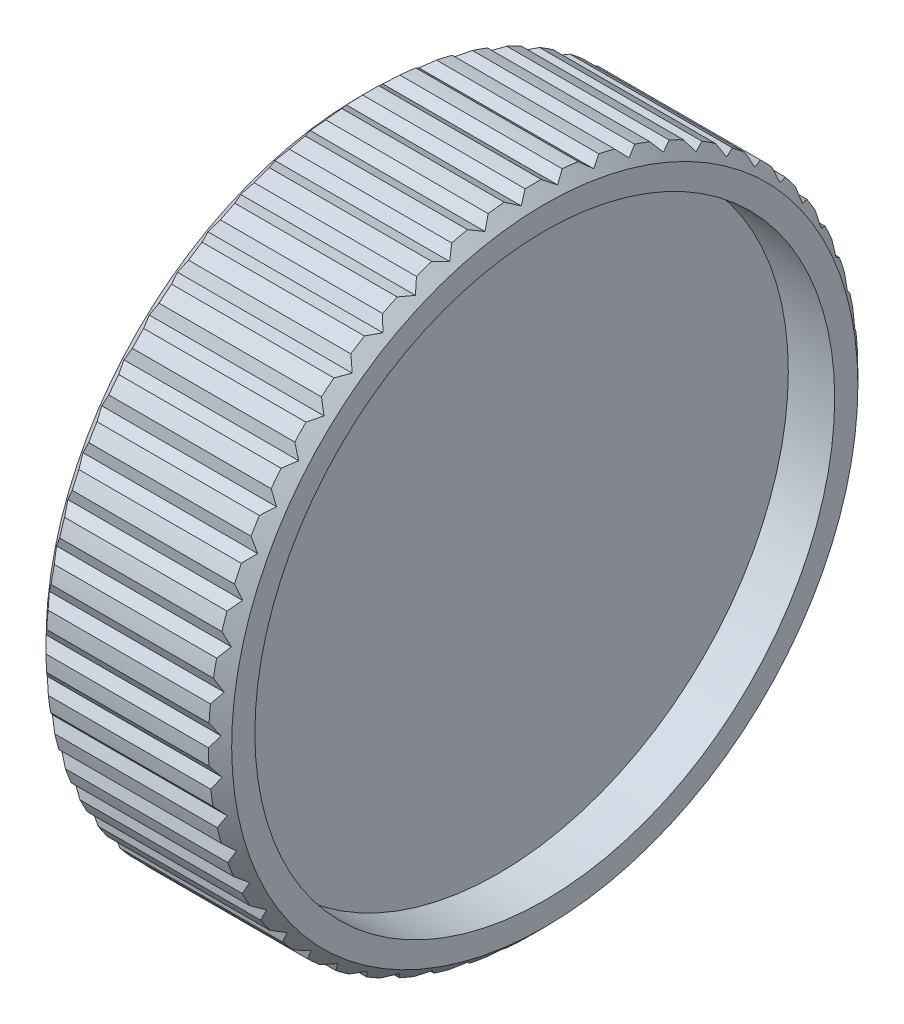
SolidWorks part; units mm, degrees
ref_plane "Front Plane" through (0, 0, 0) normal (0, 0, 1) x (1, 0, 0)
ref_plane "Top Plane" through (0, 0, 0) normal (0, 1, 0) x (1, 0, 0)
ref_plane "Right Plane" through (0, 0, 0) normal (1, 0, 0) x (0, 0, -1)
sketch "Sketch1" plane through (0, 0, 0) normal (1, 0, 0) x (0, 0, -1)
  circle A0 centre (0, 0) radius 28
  dimension "D1" = 56
extrude "Boss-Extrude1" add sketch "Sketch1" along normal mid plane 16
sketch "Sketch2" plane through (8, 0, 0) normal (1, 0, 0) x (0, 0, -1)
  circle A0 centre (0, 38) radius 15
  dimension "D1" = 30
  dimension "D2" = 38
extrude "Cut-Extrude1" [suppressed] cut sketch "Sketch2" against normal through all
chamfer "Chamfer1" distance 1 angle 45 2 edges at (-8, 0, -28) (8, 0, -28)
sketch "Sketch3" plane through (8, 0, 0) normal (1, 0, 0) x (0, 0, -1)
  circle A1 centre (0, 0) radius 25
  circle A10 centre (0, 0) radius 25
  dimension "D1" = 2
extrude "Cut-Extrude2" cut sketch "Sketch3" against normal blind 4
mirror "Mirror1" about plane through (0, 0, 0) normal (1, 0, 0) of "Cut-Extrude2"
sketch "Sketch4" plane through (8, 0, 0) normal (1, 0, 0) x (0, 0, -1)
  line L0 (0, -27.4641) -> (-8.6603, -32.4641)
  line L1 (-8.6603, -32.4641) -> (8.6603, -32.4641)
  line L2 (8.6603, -32.4641) -> (0, -27.4641)
  circle A0 centre (0, 0) radius 27 construction
  dimension "D1" = 120
  dimension "D2" = 5
extrude "Cut-Extrude3" cut sketch "Sketch4" against normal through all
pattern_circular "CirPattern1" count 55 over 360 about axis through (8, 0, 0) along (1, 0, 0) of "Cut-Extrude3" reverse direction yes
